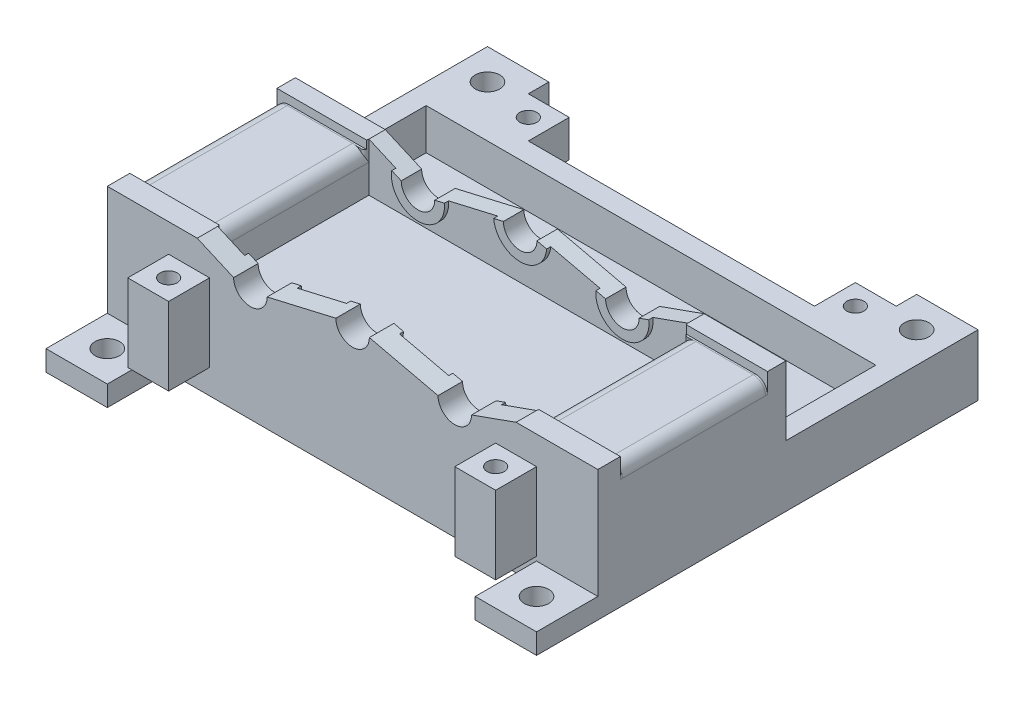
SolidWorks part; units mm, degrees
ref_plane "Спереди" through (0, 0, 0) normal (0, 0, 1) x (1, 0, 0)
ref_plane "Сверху" through (0, 0, 0) normal (0, 1, 0) x (1, 0, 0)
ref_plane "Справа" through (0, 0, 0) normal (1, 0, 0) x (0, 0, -1)
sketch "Эскиз1" plane through (0, 0, 0) normal (0, 1, 0) x (1, 0, 0)
  line L0 (-60, -17) -> (-60, 18)
  line L2 (-60, 18) -> (60, 18)
  line L12 (-60, -17) -> (60, -17)
  line L13 (60, -17) -> (60, 18)
  line L14 (-60, 18) -> (-60, 23)
  line L15 (60, 18) -> (60, 23)
  line L16 (60, 23) -> (-60, 23)
  line L17 (-60, 23) -> (-60, 55)
  line L18 (-60, 55) -> (60, 55)
  line L19 (60, 55) -> (60, 23)
  line L20 (-60, -17) -> (-60, -23)
  line L21 (-60, -23) -> (60, -23)
  line L22 (60, -23) -> (60, -17)
  line L23 (-60, 55) -> (-60, 70)
  line L25 (-45, 70) -> (-45, 55)
  line L26 (60, 55) -> (60, 70)
  line L27 (60, 70) -> (45, 70)
  line L28 (45, 70) -> (45, 55)
  line L29 (-60, -23) -> (-60, -38)
  line L30 (-60, -38) -> (-45, -38)
  line L31 (-45, -38) -> (-45, -23)
  line L32 (60, -23) -> (60, -38)
  line L33 (60, -38) -> (45, -38)
  line L34 (45, -38) -> (45, -23)
  line L35 (45, -23) -> (35, -23)
  line L36 (35, -23) -> (35, -33)
  line L37 (35, -33) -> (45, -33)
  line L38 (-45, -23) -> (-35, -23)
  line L39 (-35, -33) -> (-35, -23)
  line L40 (-35, -33) -> (-45, -33)
  line L41 (-45, 55) -> (-45, 65)
  line L42 (-35, 65) -> (-45, 65)
  line L43 (-35, 65) -> (-35, 55)
  line L44 (45, 55) -> (45, 65)
  line L45 (35, 65) -> (45, 65)
  line L46 (35, 65) -> (35, 55)
  line L47 (-60, 70) -> (-45, 70)
  circle A0 centre (-40, 60) radius 2.1
  circle A1 centre (40, 60) radius 2.1
  circle A2 centre (40, -28) radius 2.1
  circle A3 centre (-40, -28) radius 2.1
  circle A4 centre (-52.5, 62.5) radius 3
  circle A5 centre (52.5, 62.5) radius 3
  circle A6 centre (52.5, -30.5) radius 3
  circle A7 centre (-52.5, -30.5) radius 3
extrude "Бобышка-Вытянуть1" add sketch "Эскиз1" along normal blind 30 contours L12 L13 L2 L0 region at (0, 0, -0.5)
extrude "Бобышка-Вытянуть2" add sketch "Эскиз1<3>" along normal blind 40 contours L21 L22 L12 L20 | L15 L16 L14 L2 region at (0, 0, 20) region at (0, 0, -20.5)
sketch "Эскиз1<3>" plane through (0, 0, 0) normal (0, 1, 0) x (1, 0, 0) same geometry as "Эскиз1"
extrude "Бобышка-Вытянуть3" add sketch "Эскиз1<4>" along normal blind 5 contours L34 L33 L32 L21 | L27 L28 L18 L26 | L25 L23 L18 | L30 L31 L21 L29 region at (-52.5, 0, 23.2121) region at (59.7879, 0, 30.5) region at (-59.7879, 0, -62.5) region at (52.5, 0, -55.2121)
sketch "Эскиз1<4>" plane through (0, 0, 0) normal (0, 1, 0) x (1, 0, 0) same geometry as "Эскиз1"
extrude "Бобышка-Вытянуть4" add sketch "Эскиз1<5>" along normal blind 5 contours L19 L18 L17 L16 region at (0, 0, -39)
sketch "Эскиз1<5>" plane through (0, 0, 0) normal (0, 1, 0) x (1, 0, 0) same geometry as "Эскиз1"
ref_plane "Плоскость1" through (0, 30, 0) normal (0, 1, 0) x (1, 0, 0)
sketch "Эскиз4" plane through (0, 30, 0) normal (0, 1, 0) x (1, 0, 0)
  line L0 (-38, 18) -> (40, 18)
  line L1 (-60, -17) -> (60, -17) construction
  line L3 (-60, 18) -> (60, 18) construction
  line L5 (-38, 18) -> (-38, -17)
  line L6 (-60, -17) -> (60, -17) construction
  line L7 (-38, -17) -> (40, -17)
  line L8 (40, -17) -> (40, 18)
extrude "Вырез-Вытянуть2" cut sketch "Эскиз4" against normal blind 10
ref_plane "Плоскость2" through (0, 0, -18) normal (0, 0, 1) x (1, 0, 0)
fillet "Скругление7" radius 3 4 edges at (60, 30, -0.5) (40, 30, -0.5) (-60, 30, -0.5) (-38, 30, -0.5)
sketch "Эскиз5" plane through (0, 0, -18) normal (0, 0, 1) x (1, 0, 0)
  line L1 (-38, 31.9) -> (-60, 31.9)
  line L2 (-20.9, 28) -> (-4.1, 31.9)
  line L8 (60, 40) -> (60, 27) construction
  line L9 (60, 40) -> (-60, 40)
  line L13 (4.1, 31.9) -> (20.9, 28)
  line L15 (-38, 31.9) -> (-29.1, 28)
  line L16 (40, 31.9) -> (60, 31.9)
  line L18 (40, 31.9) -> (29.1, 28)
  line L19 (60, 31.9) -> (60, 40)
  line L20 (-60, 31.9) -> (-60, 40)
  arc A3 (-29.1, 28) -> (-20.9, 28) centre (-25, 28) ccw
  arc A5 (20.9, 28) -> (29.1, 28) centre (25, 28) ccw
  arc A8 (-4.1, 31.9) -> (4.1, 31.9) centre (0, 31.9) ccw
extrude "Бобышка-Вытянуть7" add sketch "Эскиз1<7>" along normal blind 25 contours L40 L39 L21 L31 A3 | L36 L37 L34 L21 A2 region at (-40, 0, 23.1414) region at (44.8586, 0, 28)
sketch "Эскиз1<7>" plane through (0, 0, 0) normal (0, 1, 0) x (1, 0, 0) same geometry as "Эскиз1"
extrude "Бобышка-Вытянуть8" add sketch "Эскиз1<8>" along normal blind 5 contours L45 L46 L18 L28 A1 | L43 L42 L25 L18 A0 region at (-44.8586, 0, -60) region at (40, 0, -55.1414)
sketch "Эскиз1<8>" plane through (0, 0, 0) normal (0, 1, 0) x (1, 0, 0) same geometry as "Эскиз1"
extrude "Вырез-Вытянуть6" cut sketch "Эскиз5" against normal through all both and the other way through all
ref_plane "Плоскость12" through (0, 0, 0) normal (0, -1, 0) x (-1, 0, 0)
sketch "Эскиз6" plane through (0, 0, 0) normal (0, -1, 0) x (-1, 0, 0)
  line L0 (-45, 65) -> (-45, 55)
  line L1 (-35, 65) -> (-45, 65) construction
  line L2 (-45, 70) -> (-45, 65) construction
  line L3 (-35, 55) -> (-45, 55)
  line L4 (-45, 65) -> (-35, 65)
  line L5 (-35, 65) -> (-35, 55)
  line L6 (35, 55) -> (45, 55)
  line L7 (45, 55) -> (45, 65)
  line L8 (45, 65) -> (35, 65)
  line L9 (35, 65) -> (35, 55)
  line L10 (35, -23) -> (45, -23)
  line L11 (45, -23) -> (45, -33)
  line L12 (45, -33) -> (35, -33)
  line L13 (35, -33) -> (35, -23)
  line L14 (-45, -33) -> (-45, -23)
  line L15 (-45, -23) -> (-35, -23)
  line L16 (-35, -23) -> (-35, -33)
  line L17 (-35, -33) -> (-45, -33) construction
  line L18 (-35, -23) -> (-35, -33) construction
  line L19 (-35, -33) -> (-45, -33)
ref_plane "Плоскость13" through (0, 5, 0) normal (0, 1, 0) x (1, 0, 0)
sketch "Эскиз7" plane through (0, 5, 0) normal (0, 1, 0) x (1, 0, 0)
  line L0 (-60, 70) -> (-60, 55)
  line L1 (-60, 23) -> (-60, 70) construction
  line L3 (-35, 55) -> (-35, 65)
  line L4 (-35, 65) -> (-45, 65)
  line L5 (-45, 65) -> (-45, 70)
  line L6 (-45, 70) -> (-60, 70)
  line L8 (60, 70) -> (60, 23) construction
  line L9 (60, 55) -> (60, 70)
  line L10 (60, 70) -> (45, 70)
  line L11 (60, 70) -> (45, 70) construction
  line L12 (45, 70) -> (45, 65)
  line L13 (45, 65) -> (35, 65)
  line L14 (35, 65) -> (35, 55)
  line L15 (-60, 55) -> (-60, 50)
  line L16 (-60, 50) -> (60, 50)
  line L17 (60, 55) -> (60, 50)
  line L18 (-35, 55) -> (35, 55)
  line L19 (-60, 50) -> (-60, 23)
  line L20 (-60, 23) -> (-55, 23)
  line L22 (-55, 23) -> (-55, 50)
  line L23 (60, 50) -> (60, 23)
  line L24 (60, 23) -> (55, 23)
  line L26 (60, 23) -> (-60, 23) construction
  line L27 (60, 55) -> (35, 55)
  line L28 (-35, 55) -> (-60, 55)
  line L29 (-55, 23) -> (-60, 23)
  line L30 (-60, 50) -> (-60, 23)
  line L31 (55, 23) -> (55, 50)
  circle A0 centre (40, 60) radius 2.1
  circle A1 centre (52.5, 62.5) radius 3
  circle A2 centre (-52.5, 62.5) radius 3
  circle A3 centre (-40, 60) radius 2.1
extrude "Бобышка-Вытянуть9" add sketch "Эскиз7" along normal blind 10 contours L23 L16 | L16 | L18 L28 L15 L16 L27 | L5 L6 L0 L28 L3 L4 A3 A2 | L13 L14 L27 L9 L10 L12 A1 A0 region at (-48.6933, 5, -61.7387) region at (0, 5, -52.5) region at (-57.5, 5, -36.5) region at (48.6933, 5, -61.7387) region at (57.5, 5, -36.5)
extrude "Вырез-Вытянуть10" cut sketch "Эскиз6" against normal blind 6
sketch "Эскиз8" plane through (0, 0, -18) normal (0, 0, 1) x (1, 0, 0)
  line L0 (-38, 20) -> (-38, 27)
  line L1 (-38, 20) -> (-38, 27) construction
  line L2 (-38, 27) -> (-38, 31.9)
  line L3 (-38, 31.9) -> (40, 31.9)
  line L4 (40, 31.9) -> (29.1, 28) construction
  line L5 (40, 31.9) -> (40, 20)
  line L6 (40, 20) -> (-38, 20) construction
  line L7 (40, 20) -> (-38, 20)
  arc A0 (-38, 27) -> (-41, 30) centre (-41, 27) ccw construction
extrude "Вырез-Вытянуть12" cut sketch "Эскиз8" along normal blind 36 and the other way blind 1
fillet "Скругление8" radius 1 4 edges at (-38, 29.45, 17) (40, 29.45, 17) (40, 29.45, -18) (-38, 29.45, -18)
ref_plane "Плоскость14" through (0, 0, -19) normal (0, 0, 1) x (1, 0, 0)
sketch "Эскиз10" plane through (0, 0, -19) normal (0, 0, 1) x (1, 0, 0)
  line L1 (-31.42, 29.0166) -> (-29.1, 28)
  line L2 (-38, 31.9) -> (-29.1, 28) construction
  line L5 (-20.9, 28) -> (-18.5235, 28.5517)
  line L8 (29.1, 28) -> (40, 31.9) construction
  line L12 (-20.9, 28) -> (-4.1, 31.9) construction
  line L14 (4.1, 31.9) -> (20.9, 28) construction
  line L15 (-6.4765, 31.3483) -> (-4.1, 31.9)
  line L16 (4.1, 31.9) -> (6.4765, 31.3483)
  line L17 (18.5235, 28.5517) -> (20.9, 28)
  line L18 (29.1, 28) -> (31.4456, 28.8392)
  arc A6 (-31.42, 29.0166) -> (-18.5235, 28.5517) centre (-25, 28) ccw
  arc A7 (-6.4765, 31.3483) -> (6.4765, 31.3483) centre (0, 31.9) ccw
  arc A8 (18.5235, 28.5517) -> (31.4456, 28.8392) centre (25, 28) ccw
  arc A9 (-29.1, 28) -> (-20.9, 28) centre (-25, 28) ccw
  arc A10 (-4.1, 31.9) -> (4.1, 31.9) centre (0, 31.9) ccw
  arc A11 (20.9, 28) -> (29.1, 28) centre (25, 28) ccw
extrude "Бобышка-Вытянуть10" add sketch "Эскиз10" along normal blind 1
ref_plane "Плоскость15" through (0, 0, 18) normal (0, 0, -1) x (-1, 0, 0)
sketch "Эскиз11" plane through (0, 0, 18) normal (0, 0, -1) x (-1, 0, 0)
  line L0 (-29.1, 28) -> (-31.4456, 28.8392)
  line L1 (-29.1, 28) -> (-40, 31.9) construction
  line L2 (-20.9, 28) -> (-18.5235, 28.5517)
  line L3 (-4.1, 31.9) -> (-20.9, 28) construction
  line L4 (-4.1, 31.9) -> (-6.4765, 31.3483)
  line L5 (4.1, 31.9) -> (6.4765, 31.3483)
  line L6 (29.1, 28) -> (31.42, 29.0166)
  line L7 (38, 31.9) -> (29.1, 28) construction
  line L8 (20.9, 28) -> (18.5235, 28.5517)
  arc A6 (18.5235, 28.5517) -> (31.42, 29.0166) centre (25, 28) ccw
  arc A7 (-6.4765, 31.3483) -> (6.4765, 31.3483) centre (0, 31.9) ccw
  arc A8 (-31.4456, 28.8392) -> (-18.5235, 28.5517) centre (-25, 28) ccw
  arc A9 (-4.1, 31.9) -> (4.1, 31.9) centre (0, 31.9) ccw
  arc A10 (20.9, 28) -> (29.1, 28) centre (25, 28) ccw
  arc A11 (-29.1, 28) -> (-20.9, 28) centre (-25, 28) ccw
extrude "Бобышка-Вытянуть11" add sketch "Эскиз11" along normal blind 1
ref_plane "Плоскость16" through (0, 31.9, 0) normal (0, 1, 0) x (1, 0, 0)
sketch "Эскиз12" plane through (0, 31.9, 0) normal (0, 1, 0) x (1, 0, 0)
  line L0 (-38, 18) -> (-38, 18.4994)
  line L1 (-2.695, 18) -> (2.695, 18) construction
  line L2 (-38, 19) -> (-38, -18) construction
  line L3 (-38, 18.4994) -> (-60, 18.4994)
  line L4 (-60, 23) -> (-60, 18) construction
  line L5 (-60, 18.4994) -> (-60, 18)
  line L6 (-60, 18) -> (-38, 18)
  line L7 (-60, -17) -> (-60, -17.5)
  line L8 (-60, -17) -> (-60, -23) construction
  line L9 (-60, -17.5) -> (-38, -17.5)
  line L10 (-38, -17.5) -> (-38, -17)
  line L11 (-38, -17) -> (-60, -17)
  line L12 (60, 18) -> (60, 18.5)
  line L13 (57, 18) -> (60, 18) construction
  line L14 (60, 23) -> (60, 18) construction
  line L15 (60, 18.5) -> (40, 18.5)
  line L16 (40, -18) -> (40, 19) construction
  line L17 (40, 18.5) -> (40, 18)
  line L18 (40, 18) -> (60, 18)
  line L19 (60, -17) -> (60, -17.5)
  line L20 (60, -17) -> (60, -23) construction
  line L21 (60, -17.5) -> (40, -17.5)
  line L22 (40, -17.5) -> (40, -17)
  line L23 (40, -17) -> (60, -17)
extrude "Вырез-Вытянуть13" cut sketch "Эскиз12" against normal blind 2
fillet "Скругление10" radius 2.9 4 edges at (-60, 29.9, -18.2497) (-60, 29.9, 17.25) (60, 29.9, 17.25) (60, 29.9, -18.25)
ref_plane "Плоскость17" through (0, 20, 0) normal (0, 1, 0) x (1, 0, 0)
